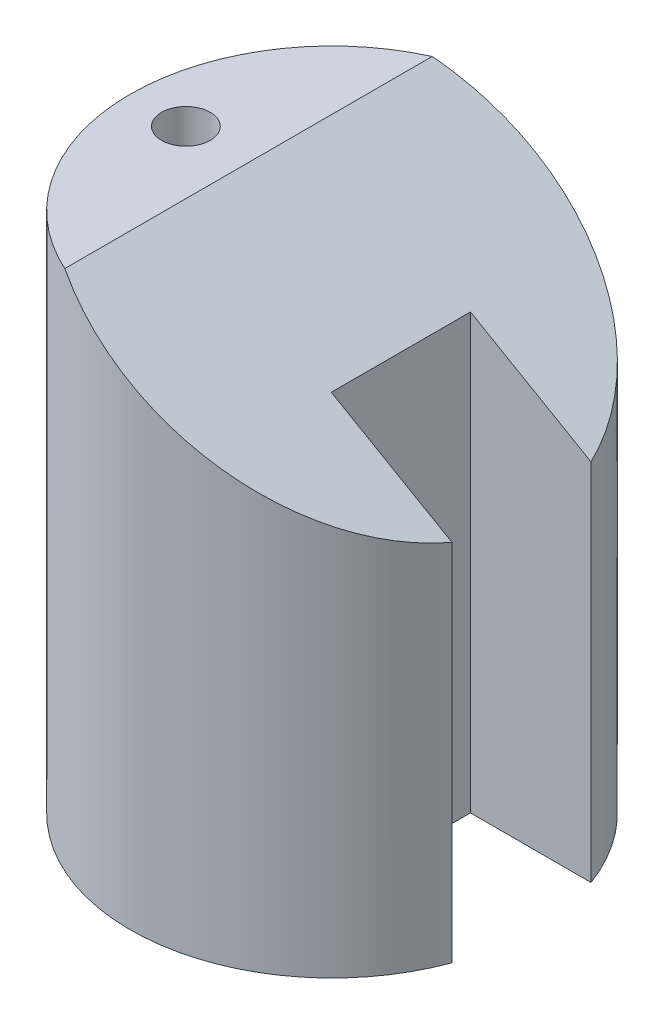
SolidWorks part; units mm, degrees
material "Cast Alloy Steel"
ref_plane "Front Plane" through (0, 0, 0) normal (0, 0, 1) x (1, 0, 0)
ref_plane "Top Plane" through (0, 0, 0) normal (0, 1, 0) x (1, 0, 0)
ref_plane "Right Plane" through (0, 0, 0) normal (1, 0, 0) x (0, 0, -1)
sketch "Sketch1" plane through (0, 0, 0) normal (0, 1, 0) x (1, 0, 0)
  circle A2 centre (0, 0) radius 29
  dimension "D1" = 58
extrude "Boss-Extrude1" add sketch "Sketch1" along normal blind 75
sketch "Sketch2" plane through (0, 75, 0) normal (0, 1, 0) x (1, 0, 0)
  line L0 (0, 43.2576) -> (0, -47.6197) construction
  line L1 (-46.9484, 0) -> (43.2672, 0) construction
  line L2 (-12, 26.4008) -> (-12, -26.4008)
  circle A0 centre (0, 0) radius 29 construction
  arc A1 (-12, 26.4008) -> (-12, -26.4008) centre (0, 0) ccw
  point P9 (-11.4411, -26.6477)
  dimension "D1" = 12
sketch "Sketch3" plane through (0, 75, 0) normal (0, 1, 0) x (1, 0, 0)
  line L0 (-46.9484, 0) -> (43.2672, 0) construction
  line L1 (-12, 26.4008) -> (-12, -26.4008) construction
  circle A0 centre (-21, 0) radius 3.5
  dimension "D2" = 7
  dimension "D1" = 9
extrude "Boss-Extrude3" add sketch "Sketch3" against normal blind 50
extrude "Cut-Extrude1" cut sketch "Sketch3<4>" against normal blind 50
sketch "Sketch3<4>" plane through (0, 75, 0) normal (0, 1, 0) x (1, 0, 0) same geometry as "Sketch3"
sketch "Sketch9" plane through (0, 0, 0) normal (0, 0, 1) x (1, 0, 0)
  line L0 (-46.9484, 75) -> (43.2672, 75) construction
  line L1 (29, 0) -> (29, 75) construction
  line L2 (-12, 75) -> (29, 75)
  line L3 (29, 51.3286) -> (29, 75)
  line L4 (-12, 75) -> (-29, 75) construction
  line L5 (-12, 75) -> (29, 51.3286)
  line L6 (0, 88.2669) -> (0, -42.6609) construction
  dimension "D1" = 12
  dimension "D2" = 30
extrude "Cut-Extrude2" cut sketch "Sketch9" along normal through all both and the other way through all
sketch "Sketch18" plane through (29.476, 51.0538, 0) normal (0.5, 0.866, 0) x (0.866, -0.5, 0)
  line L0 (-78.1585, 0) -> (-0.0295, 0) construction
  line L1 (-2.6034, 10) -> (-22.6034, 10)
  line L3 (-2.6034, -10) -> (-22.6034, -10)
  line L4 (-22.6034, 10) -> (-22.6034, -10)
  ellipse E0 centre (-34.0359, 0) end of major axis (-0.5496, 0) minor radius 29 (-47.8923, -26.4008) -> (-47.8923, 26.4008) ccw construction
  ellipse E3 centre (-34.0359, 0) end of major axis (-0.5496, 0) minor radius 29 (-2.6034, -10) -> (-2.6034, 10) ccw
  point P0 (-0.5496, 0)
  dimension "D1" = 20
  dimension "D2" = 20
  dimension "D3" = 20
extrude "Cut-Extrude4" cut sketch "Sketch18" along direction (0, 1, 0) on the side against the normal through all
